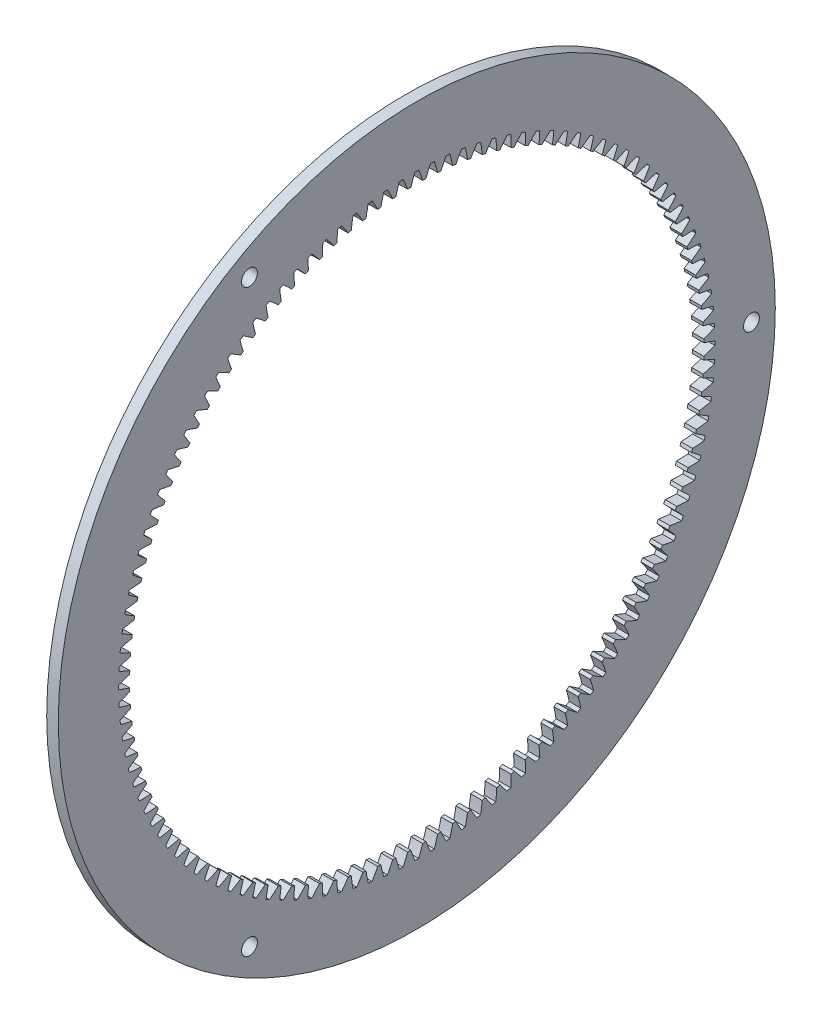
SolidWorks part; units mm, degrees
ref_plane "Plane1" through (0, 0, 0) normal (0, 0, 1) x (1, 0, 0)
ref_plane "Plane2" through (0, 0, 0) normal (0, 1, 0) x (1, 0, 0)
ref_plane "Plane3" through (0, 0, 0) normal (1, 0, 0) x (0, 0, -1)
sketch "HoldingSke" plane through (0, 0, 0) normal (0, 1, 0) x (1, 0, 0)
  line L0 (0, 0) -> (-0.25, -0.433)
  line L1 (-15, 0) -> (100, 0) construction
  line L2 (0, 0) -> (-2.1039, 2.3779)
  line L3 (0, 0) -> (-11.863, 4.5341)
  line L4 (0, 0) -> (-4.318, 7.479)
  line L5 (0, 0) -> (-23.7986, -8.8762)
  line L6 (0, 0) -> (-10.5278, -7.1032)
  line L7 (-2.1039, 2.3779) -> (3.3635, 27.1825)
  line L8 (-76.2, 4.3779) -> (-54.61, 4.3779)
  line L9 (-71.009, 38.7566) -> (-53.1078, 45.2721)
  line L10 (-76.2, 71.12) -> (104.1128, 71.12)
  line L11 (0, 0) -> (-4.7625, 0)
  line L12 (-76.2, 101.6) -> (-76.133, 101.6)
  line L13 (24.9733, 27.94) -> (52.9518, 28.4284)
  line L14 (24.9733, 27.94) -> (24.9743, 27.94)
  line L15 (24.9733, 27.94) -> (100.4006, 29.5858)
  circle A0 centre (0, 0) radius 147.32
  circle A1 centre (0, 0) radius 12.7
  circle A2 centre (0, 0) radius 12.7
  dimension "MHD" = 25.4
  dimension "Hub_dia" = 25.4
  dimension "Diameter" = 294.64
  dimension "Num_teeth" = 120
  dimension "Pitch_radius" = 180.3128
  dimension "Pitch" = 0.5
  dimension "Width" = 4.7625
  dimension "Overall_len" = 25.4
  dimension "Show_teeth" = 120
  dimension "Thickness" = 12.7
  dimension "OAL" = 25.4001
  dimension "T_dim" = 21.59
  dimension "Ap" = 20
  dimension "H" = 19.05
  dimension "Backlash" = 0.067
  dimension "Addendum_fac" = 1
  dimension "Dedendum_fac" = 1.25
  dimension "Clearance_fac" = 0.25
  dimension "Dedendum_add" = 0.001
  dimension "Module" = 2
sketch "BasProSke" plane through (0, 0, 0) normal (0, 1, 0) x (1, 0, 0)
  line L0 (-10, 0) -> (60, 0) construction
  line L1 (0, 118) -> (0, 147.32)
  line L2 (0, 118) -> (4.7625, 118)
  line L3 (4.7625, 118) -> (4.7625, 147.32)
  line L4 (4.7625, 147.32) -> (0, 147.32)
  dimension "Diameter" = 294.64
  dimension "Thickness" = 4.7625
  dimension "Inside_diameter" = 236
revolve "Base-Revolve" add sketch "BasProSke" angle 360 about L0
sketch "TooCutSke" plane through (0, 0, 0) normal (1, 0, 0) x (0, 0, -1)
  line L3 (1.7383, 119.9874) -> (1.7383, 53.6633) construction
  line L4 (0, 0) -> (0, 59.563) construction
  line L5 (0, 0) -> (-1.7886, 68.3041) construction
  line L6 (-54.8647, 100.0849) -> (35.1732, 102.4426) construction
  circle A0 centre (0, 0) radius 120 construction
  circle A1 centre (0, 0) radius 122.501 construction
  circle A2 centre (0, 0) radius 101.4868 construction
  circle A3 centre (0, 0) radius 117.9746 construction
  arc A4 (2.414, 117.9499) -> (0.7917, 122.4984) centre (-54.8647, 100.0849) ccw
  arc A5 (2.414, 117.9499) -> (-2.414, 117.9499) centre (0, 0) ccw
  arc A6 (0.7917, 122.4984) -> (-0.7917, 122.4984) centre (0, 0) ccw
  arc A7 (-0.7917, 122.4984) -> (-2.414, 117.9499) centre (54.8647, 100.0849) ccw
  dimension "Pitch_dia" = 240
  dimension "Base_dia" = 202.9736
  dimension "Root_dia" = 245.002
  dimension "Overcut_dia" = 235.9492
  dimension "Flank_rad" = 60
  dimension "Half_ang" = 1.5
  dimension "Half_CT" = 1.7383
extrude "ToothCut" cut sketch "TooCutSke" along normal through all
fillet "Breaks" [suppressed] radius 0.2
fillet "RootFillets" [suppressed] radius 0.501
pattern_circular "TeethCuts" count 120 every 3 about axis through (-10, 0, 0) along (1, 0, 0) of "RootFillets", "Breaks", "ToothCut"
sketch "Sketch1" plane through (4.7625, 0, 0) normal (1, 0, 0) x (0, 0, -1)
  line L1 (0, 158.7713) -> (-137.5, 79.3857) construction
  line L2 (-137.5, 79.3857) -> (-137.5, -79.3857) construction
  line L3 (-137.5, -79.3857) -> (0, -158.7713) construction
  line L4 (0, -158.7713) -> (137.5, -79.3857) construction
  line L5 (137.5, -79.3857) -> (137.5, 79.3857) construction
  line L6 (137.5, 79.3857) -> (0, 158.7713) construction
  circle A0 centre (0, 0) radius 137.5 construction
  circle A1 centre (-68.75, 119.0785) radius 3.2639
  circle A2 centre (137.5, 0) radius 3.2639
  circle A3 centre (-68.75, -119.0785) radius 3.2639
  point P23 (0, 0)
  dimension "D2" = 6.5278
  dimension "D4" = 137.5
  dimension "D1" = 158.7713
  dimension "D3" = 3
extrude "Cut-Extrude1" cut sketch "Sketch1" against normal through all
equation "' \"Module@HoldingSke\" = 6.35"
equation "' \"Num_teeth@HoldingSke\" = 24"
equation "' \"Ap@HoldingSke\" =  14.5"
equation "' \"Width@HoldingSke\" = 12"
equation "' \"Diameter@HoldingSke\" = 8 * 25.4"
equation "' \"Show_teeth@HoldingSke\" = 100"
equation "' \"Backlash@HoldingSke\" = 0.009 * 25.4"
equation "' \"Addendum_fac@HoldingSke\" = 1.0"
equation "' \"Dedendum_fac@HoldingSke\" = 1.25"
equation "' \"Dedendum_add@HoldingSke\" = 0.00005 * 25.4"
equation "' \"Clearance_fac@HoldingSke\" = 0.25"
equation "\"Pitch@HoldingSke\" = 1 / \"Module@HoldingSke\" "
equation "\"Overcut_dia@TooCutSke\" = (\"Num_teeth@HoldingSke\" - 2 * \"Addendum_fac@HoldingSke\") / \"Pitch@HoldingSke\" - 0.002 * 25.4"
equation "\"Pitch_dia@TooCutSke\" = \"Num_teeth@HoldingSke\" / \"Pitch@HoldingSke\""
equation "\"Base_dia@TooCutSke\" = \"Num_teeth@HoldingSke\" / \"Pitch@HoldingSke\" * cos((\"Ap@HoldingSke\"  * 3.14159265 / 180)) * 0.90"
equation "\"Root_dia@TooCutSke\" = \"Num_teeth@HoldingSke\"  / \"Pitch@HoldingSke\" + 2 *  \"Dedendum_fac@HoldingSke\"/ \"Pitch@HoldingSke\" + \"Dedendum_add@HoldingSke\" * 2"
equation "\"Half_ang@TooCutSke\" = 180 / \"Num_teeth@HoldingSke\""
equation "\"Half_CT@TooCutSke\" = \"Num_teeth@HoldingSke\" / \"Pitch@HoldingSke\" * sin((3.14159265 / 2 / \"Num_teeth@HoldingSke\")) / 2 + 10 * \"Backlash@HoldingSke\" / 4"
equation "\"Flank_rad@TooCutSke\" = \"Num_teeth@HoldingSke\" / \"Pitch@HoldingSke\" / 4"
equation "\"Radius@RootFillets\"= \"Clearance_fac@HoldingSke\" / \"Pitch@HoldingSke\" + \"Dedendum_add@HoldingSke\""
equation "\"Break_rad@Breaks\" = 0.02 / \"Pitch@HoldingSke\" * 5"
equation "\"Num_teeth@TeethCuts\" = int( \"Show_teeth@HoldingSke\" ) + 1"
equation "\"Num_teeth@TeethCuts\" = ((sgn( \"Num_teeth@TeethCuts\" - \"Num_teeth@HoldingSke\" )-1)*( \"Num_teeth@TeethCuts\" - \"Num_teeth@HoldingSke\" ))/-2+ \"Num_teeth@HoldingSke\""
equation "\"Num_teeth@TeethCuts\" = ((sgn( \"Num_teeth@TeethCuts\" - 2.0)+1)*( \"Num_teeth@TeethCuts\" - 2.0))/2 +2.0"
equation "\"Angle@TeethCuts\" = 360.0 / \"Num_teeth@HoldingSke\""
equation "\"Diameter@BasProSke\" = \"Num_teeth@HoldingSke\"  / \"Pitch@HoldingSke\" + 2 *  \"Dedendum_fac@HoldingSke\"/ \"Pitch@HoldingSke\" + \"Dedendum_add@HoldingSke\" * 2 + 0.002 * 25.4"
equation "\"Diameter@BasProSke\" = ((sgn( \"Diameter@BasProSke\"  - \"Diameter@HoldingSke\" )+1)*( \"Diameter@BasProSke\"  - \"Diameter@HoldingSke\" ))/2 + \"Diameter@HoldingSke\""
equation "\"Inside_diameter@BasProSke\" =  (\"Num_teeth@HoldingSke\" - 2 * \"Addendum_fac@HoldingSke\") / \"Pitch@HoldingSke\" "
equation "\"Thickness@BasProSke\"  = \"Width@HoldingSke\""
equation "\"D1@Sketch1\"=6.25083953in"
